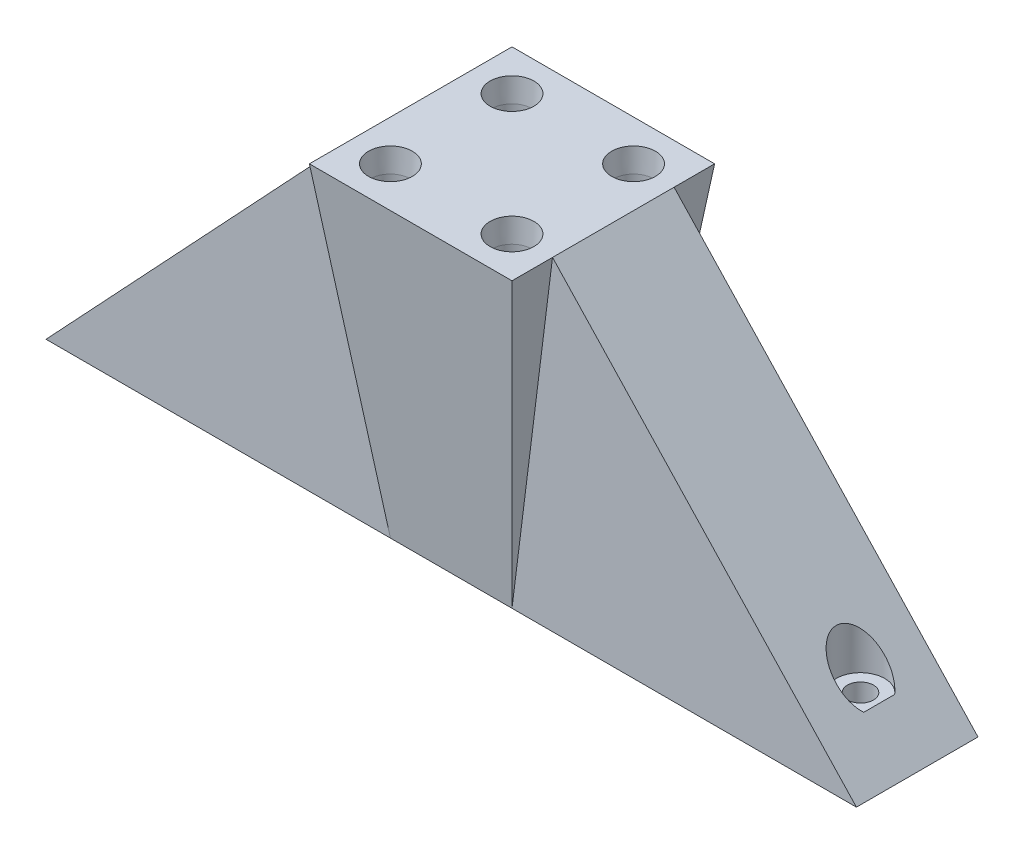
SolidWorks part; units mm, degrees
ref_plane "Front Plane" through (0, 0, 0) normal (0, 0, 1) x (1, 0, 0)
ref_plane "Top Plane" through (0, 0, 0) normal (0, 1, 0) x (1, 0, 0)
ref_plane "Right Plane" through (0, 0, 0) normal (1, 0, 0) x (0, 0, -1)
sketch "Sketch2" plane through (0, 0, 0) normal (0, 1, 0) x (1, 0, 0)
  line L1 (-50, 7.5) -> (50, 7.5)
  line L2 (-50, 7.5) -> (-50, -7.5)
  line L3 (-50, -7.5) -> (50, -7.5)
  line L4 (50, 7.5) -> (50, -7.5)
  line L5 (-50, 7.5) -> (50, -7.5) construction
  line L6 (-50, -7.5) -> (50, 7.5) construction
  line L7 (-7.5, 7.5) -> (7.5, 7.5)
  line L8 (-7.5, 7.5) -> (-7.5, -7.5)
  line L9 (-7.5, -7.5) -> (7.5, -7.5)
  line L10 (7.5, 7.5) -> (7.5, -7.5)
  line L11 (-7.5, 7.5) -> (7.5, -7.5) construction
  line L12 (-7.5, -7.5) -> (7.5, 7.5) construction
  point P0 (0, 0)
  point P6 (0, 0)
  dimension "D1" = 15
  dimension "D2" = 100
  dimension "D3" = 15
extrude "Boss-Extrude1" add sketch "Sketch2" along normal blind 40 draft 7.125 contours L10 L1 L8 L3 region at (0, 0, 0) draft outward yes
extrude "Boss-Extrude4" add sketch "Sketch2<4>" along normal up to surface (40 mm away) contours L8 L1 L2 L3 | L1 L10 L3 L4 region at (-28.75, 0, 0) region at (28.75, 0, 0) up to face at (0, 40, 0)
sketch "Sketch2<4>" plane through (0, 0, 0) normal (0, 1, 0) x (1, 0, 0) same geometry as "Sketch2"
sketch "Sketch4" plane through (0, 0, -7.5) normal (0, 0, -1) x (-1, 0, 0)
  line L0 (-12.5, 40) -> (-50, 0)
  line L1 (-50, 0) -> (-50, 40)
  line L2 (-50, 40) -> (-12.5, 40)
extrude "Cut-Extrude1" cut sketch "Sketch4" against normal up to next
sketch "Sketch5" plane through (0, 0, 0) normal (0, -1, 0) x (1, 0, 0)
  line L0 (50, -7.5) -> (50, 7.5) construction
  circle A0 centre (43, 0) radius 1.6
  circle A1 centre (43, 0) radius 3
  dimension "D2" = 3.2
  dimension "D3" = 6
  dimension "D1" = 7
extrude "Cut-Extrude2" cut sketch "Sketch5" against normal up to surface (2.4667 mm away) from offset 5 contours A0 | A1 A0 region at (43, 0, 0) region at (40.0849, 0, 0) up to face at (31.25, 20, 0) offset against normal yes
extrude "Cut-Extrude3" cut sketch "Sketch5<3>" against normal through all contours A0 region at (43, 0, 0)
sketch "Sketch5<3>" plane through (0, 0, 0) normal (0, -1, 0) x (1, 0, 0) same geometry as "Sketch5"
mirror "Mirror1" about plane through (0, 0, 0) normal (1, 0, 0) of "Cut-Extrude2", "Cut-Extrude1", "Cut-Extrude3"
hole_wizard "CSK for M3 Oval Head Machine Screw1" positions "Sketch7" profile "Sketch8" countersink size "M3" standard "ANSI Metric"
sketch "Sketch7" plane through (0, 40, 0) normal (0, 1, 0) x (1, 0, 0)
  line L0 (-12.5, 12.5) -> (12.5, 12.5) construction
  line L1 (-12.5, 12.5) -> (-12.5, 7.5) construction
  point P0 (-7.5, 7.5)
  dimension "D1" = 5
  dimension "D2" = 5
sketch "Sketch8" plane through (-7.5, 40, -7.5) normal (1, 0, 0) x (0, 0, 1)
  line L0 (0, 0) -> (0, 11.5022)
  line L1 (0, 11.5022) -> (2.5, 10)
  line L2 (2.5, 10) -> (2.5, 2.8601)
  line L3 (2.5, 2.8601) -> (2.7, 0)
  line L5 (2.7, 0) -> (0, 0)
  line L6 (-2.5, 2.8601) -> (-2.7, 0) construction
  line L10 (0, 11.5022) -> (-2.5, 10) construction
  line L11 (0, -6.35) -> (0, 107.95) construction
  dimension "Hole Dia." = 5
  dimension "Hole Depth" = 10
  dimension "Near C'Sink Dia." = 5.4
  dimension "Near C'Sink Angle" = 8
  dimension "Drill Angle" = 118
pattern_linear "LPattern1" count 2 spacing 15 along (0, 0, 1) count 2 spacing 15 along (1, 0, 0) of "CSK for M3 Oval Head Machine Screw1"
